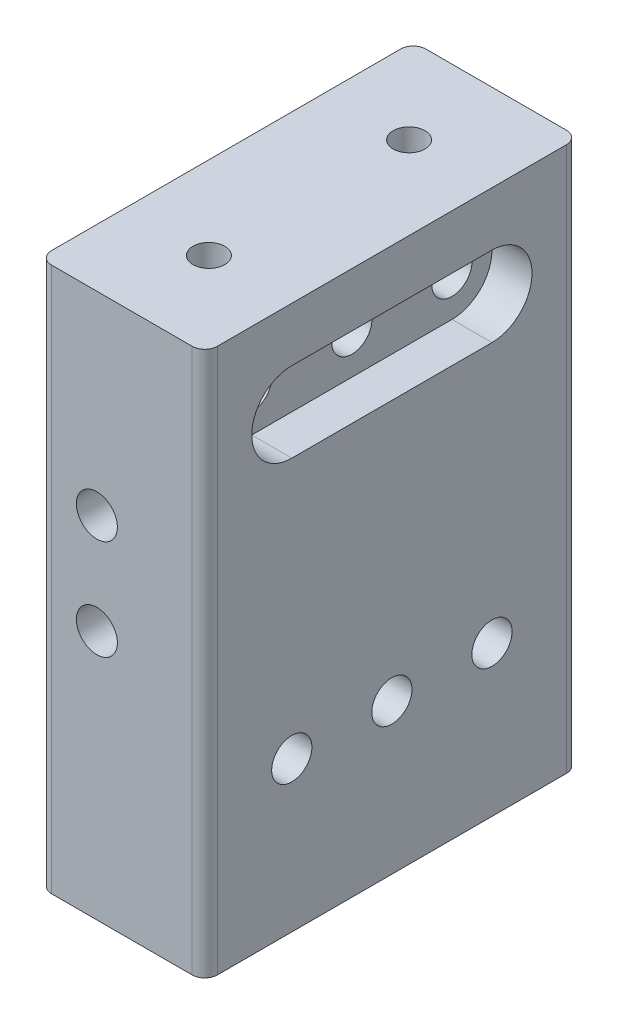
SolidWorks part; units mm, degrees
material "PET"
ref_plane "Front Plane" through (0, 0, 0) normal (0, 0, 1) x (1, 0, 0)
ref_plane "Top Plane" through (0, 0, 0) normal (0, 1, 0) x (1, 0, 0)
ref_plane "Right Plane" through (0, 0, 0) normal (1, 0, 0) x (0, 0, -1)
sketch "Sketch1" plane through (0, 0, 0) normal (0, 1, 0) x (1, 0, 0)
  line L1 (-10.5156, -23.7427) -> (10.5156, -23.7427)
  line L2 (-10.5156, -23.7427) -> (-10.5156, 23.7426)
  line L3 (-10.5156, 23.7426) -> (10.5156, 23.7426)
  line L4 (10.5156, -23.7427) -> (10.5156, 23.7426)
  line L5 (-10.5156, -23.7427) -> (10.5156, 23.7426) construction
  line L6 (-10.5156, 23.7426) -> (10.5156, -23.7427) construction
  point P0 (0, 0)
  dimension "D1" = 21.0312
  dimension "D2" = 47.4853
extrude "Boss-Extrude1" add sketch "Sketch1" along normal mid plane 63.5
sketch "Sketch2" plane through (0, 0, 23.7427) normal (0, 0, 1) x (1, 0, 0)
  line L5 (-10.5156, 31.75) -> (10.5156, 31.75) construction
  circle A1 centre (-3.175, 0) radius 2.6035
  circle A2 centre (-3.175, 12.7) radius 2.6035
  circle A3 centre (-3.175, -12.7) radius 2.6035
  dimension "D3" = 19.05
  dimension "D1" = 13.6906
  dimension "D2" = 5.207
  dimension "D4" = 12.7
  dimension "D5" = 12.7
extrude "Cut-Extrude1" cut sketch "Sketch2" against normal through all contours A2 | A1 region at (-3.175, 0, 23.7427) region at (-3.175, 12.7, 23.7427)
sketch "Sketch4" plane through (10.5156, 0, 0) normal (1, 0, 0) x (0, 0, -1)
  line L0 (-23.7427, 31.75) -> (23.7426, 31.75) construction
  circle A0 centre (-12.7, 25.4) radius 2.5527
  circle A1 centre (12.7, 25.4) radius 2.5527
  circle A2 centre (0, 25.4) radius 2.5527
  dimension "D5" = 5.1054
  dimension "D1" = 6.35
  dimension "D3" = 12.7
  dimension "D4" = 12.7
extrude "Cut-Extrude3" cut sketch "Sketch4" against normal through all
fillet "Fillet1" radius 1.5875 4 edges at (10.5156, 0, 23.7427) (-10.5156, 0, 23.7427) (-10.5156, 0, -23.7426) (10.5156, 0, -23.7426)
sketch "Sketch7" plane through (10.5156, 0, 0) normal (1, 0, 0) x (0, 0, -1)
  line L0 (-12.7, 25.4) -> (12.7, 25.4) construction
  line L1 (-12.7, 30.48) -> (12.7, 30.48)
  line L2 (-12.7, 20.32) -> (12.7, 20.32)
  arc A0 (-12.7, 30.48) -> (-12.7, 20.32) centre (-12.7, 25.4) ccw
  arc A1 (12.7, 20.32) -> (12.7, 30.48) centre (12.7, 25.4) ccw
  point P4 (0, 25.4)
  dimension "D1" = 5.08
extrude "Cut-Extrude5" cut sketch "Sketch7" against normal blind 5.08
sketch "Sketch8" plane through (0, 31.75, 0) normal (0, 1, 0) x (1, 0, 0)
  line L4 (-8.9281, -23.7427) -> (8.9281, -23.7427)
  line L5 (10.5156, -22.1552) -> (10.5156, 22.1551)
  line L6 (8.9281, 23.7426) -> (-8.9281, 23.7426)
  line L7 (-10.5156, 22.1551) -> (-10.5156, -22.1552)
  line L8 (-8.9281, -23.7427) -> (8.9281, -23.7427)
  line L9 (10.5156, -22.1552) -> (10.5156, 22.1551)
  line L10 (8.9281, 23.7426) -> (-8.9281, 23.7426)
  line L11 (-10.5156, 22.1551) -> (-10.5156, -22.1552)
  arc A4 (8.9281, -23.7427) -> (10.5156, -22.1552) centre (8.9281, -22.1552) ccw
  arc A5 (10.5156, 22.1551) -> (8.9281, 23.7426) centre (8.9281, 22.1551) ccw
  arc A6 (-8.9281, 23.7426) -> (-10.5156, 22.1551) centre (-8.9281, 22.1551) ccw
  arc A7 (-8.9281, 23.7426) -> (-10.5156, 22.1551) centre (-8.9281, 22.1551) ccw
  arc A8 (8.9281, -23.7427) -> (10.5156, -22.1552) centre (8.9281, -22.1552) ccw
  arc A9 (10.5156, 22.1551) -> (8.9281, 23.7426) centre (8.9281, 22.1551) ccw
  arc A10 (-10.5156, -22.1552) -> (-8.9281, -23.7427) centre (-8.9281, -22.1552) ccw
  arc A11 (-10.5156, -22.1552) -> (-8.9281, -23.7427) centre (-8.9281, -22.1552) ccw
  dimension "D1" = 0
extrude "Boss-Extrude2" add sketch "Sketch8" along normal blind 5.588
sketch "Sketch9" plane through (0, 37.338, 0) normal (0, 1, 0) x (1, 0, 0)
  line L0 (-10.5156, 0) -> (10.5156, 0) construction
  line L1 (-10.5156, 22.1551) -> (-10.5156, -22.1552) construction
  line L2 (10.5156, -22.1552) -> (10.5156, 22.1551) construction
  circle A0 centre (0, 12.7) radius 2.0193
  circle A2 centre (0, -12.7) radius 2.0193
  dimension "D2" = 4.0386
  dimension "D1" = 12.7
  dimension "D3" = 10.5156
extrude "Cut-Extrude6" cut sketch "Sketch9" against normal blind 5.08
sketch "Sketch10" plane through (10.5156, 0, 0) normal (1, 0, 0) x (0, 0, -1)
  line L1 (-22.1552, -31.75) -> (22.1551, -31.75) construction
  circle A0 centre (0, -12.7) radius 2.5527
  circle A1 centre (12.7, -12.7) radius 2.5527
  circle A2 centre (-12.7, -12.7) radius 2.5527
  dimension "D1" = 5.1054
  dimension "D2" = 12.7
  dimension "D3" = 12.7
  dimension "D4" = 19.05
extrude "Cut-Extrude7" cut sketch "Sketch10" against normal through all
sketch "Sketch11" plane through (-10.5156, 0, 0) normal (-1, 0, 0) x (0, 0, 1)
  line L0 (-12.7, -12.7) -> (12.7, -12.7) construction
  line L1 (-12.7, -3.2448) -> (12.7, -3.2448)
  line L2 (-12.7, -22.1552) -> (12.7, -22.1552)
  line L3 (22.1552, -31.75) -> (22.1552, 37.338) construction
  arc A0 (-12.7, -3.2448) -> (-12.7, -22.1552) centre (-12.7, -12.7) ccw
  arc A1 (12.7, -22.1552) -> (12.7, -3.2448) centre (12.7, -12.7) ccw
  point P4 (0, -12.7)
extrude "Cut-Extrude8" cut sketch "Sketch11" against normal blind 7.9375
